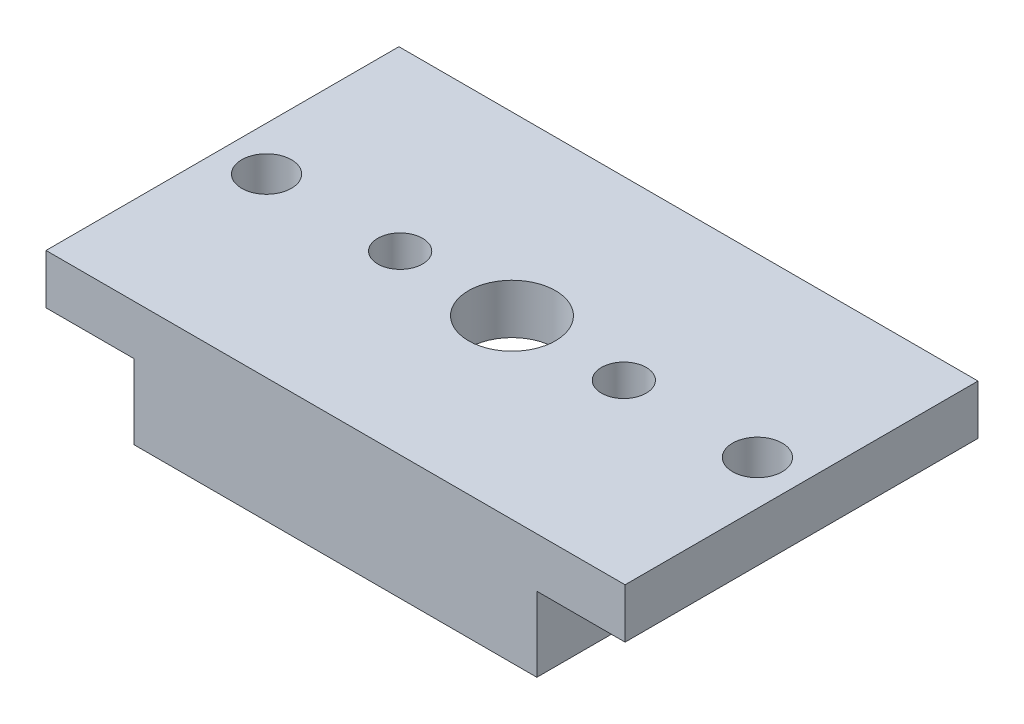
SolidWorks part; units mm, degrees
other "标注1"
sketch "草图3" plane through (-22.25, 4, -10) normal (-0.231, 0.6469, -0.7268) x (-0.9696, -0.2151, 0.1167)
ref_plane "前视基准面" through (0, 0, 0) normal (0, 0, 1) x (1, 0, 0)
ref_plane "上视基准面" through (0, 0, 0) normal (0, 1, 0) x (1, 0, 0)
ref_plane "右视基准面" through (0, 0, 0) normal (1, 0, 0) x (0, 0, -1)
other "Configuration Table"
sketch "草图4" plane through (0, 0, 0) normal (0, 1, 0) x (1, 0, 0)
  line L0 (-4.5, 0) -> (0, 0) construction
  line L1 (-8.1, -7.1) -> (8.1, -7.1)
  line L2 (-8.1, -7.1) -> (-8.1, 7.1)
  line L3 (-8.1, 7.1) -> (8.1, 7.1)
  line L4 (8.1, -7.1) -> (8.1, 7.1)
  line L5 (-8.1, -7.1) -> (8.1, 7.1) construction
  line L6 (-8.1, 7.1) -> (8.1, -7.1) construction
  line L7 (-6.1, 5.1) -> (6.1, 5.1)
  line L8 (-6.1, 5.1) -> (-6.1, -5.1)
  line L9 (-6.1, -5.1) -> (6.1, -5.1)
  line L10 (6.1, 5.1) -> (6.1, -5.1)
  line L11 (0, 0) -> (4.5, 0) construction
  circle A0 centre (0, 0) radius 1.75
  circle A1 centre (-4.5, 0) radius 0.9
  circle A2 centre (4.5, 0) radius 0.9
  point P0 (0, 0)
  dimension "D1" = 2
  dimension "D2" = 2
  dimension "D3" = 3.5
  dimension "D8" = 1.8
  dimension "D9" = 1.8
  dimension "D4" = 2
  dimension "D5" = 2
  dimension "D6" = 12.2
  dimension "D7" = 10.2
  dimension "D10" = 4.5
extrude "凸台-拉伸1" add sketch "草图4" along normal blind 2 contours A2 | L1 L4 L3 L2 | A0 | A1 region at (4.5, 0, 0)
extrude "凸台-拉伸2" add sketch "草图4<8>" against normal blind 3 contours L1 L4 L3 L2 L7 L10 L9 L8 region at (-7.8846, 0, 0)
sketch "草图4<8>" plane through (0, 0, 0) normal (0, 1, 0) x (1, 0, 0) same geometry as "草图4"
sketch "草图5" plane through (0, 2, 0) normal (0, 1, 0) x (1, 0, 0)
  line L0 (-8.1, 7.1) -> (8.1, 7.1) construction
  line L1 (11.65, -7.1) -> (-11.65, -7.1)
  line L2 (11.65, -7.1) -> (11.65, 7.1)
  line L3 (11.65, 7.1) -> (-11.65, 7.1)
  line L4 (-11.65, -7.1) -> (-11.65, 7.1)
  line L5 (-8.1, -7.1) -> (8.1, -7.1) construction
  line L6 (11.65, 0) -> (-11.65, 0) construction
  line L7 (8.1, -7.1) -> (8.1, 7.1) construction
  line L8 (-6.1, 5.1) -> (6.1, 5.1) construction
  line L9 (6.1, 5.1) -> (-6.1, 5.1)
  line L10 (6.1, 5.1) -> (6.1, -5.1)
  line L11 (6.1, -5.1) -> (-6.1, -5.1)
  line L12 (-6.1, 5.1) -> (-6.1, -5.1)
  line L13 (-6.1, -5.1) -> (6.1, -5.1) construction
  line L14 (6.1, 5.1) -> (6.1, -5.1) construction
  line L15 (-6.1, 5.1) -> (-6.1, -5.1) construction
  dimension "D1" = 3.55
extrude "凸台-拉伸3" add sketch "草图5" against normal blind 2
sketch "草图6" plane through (0, 0, 0) normal (0, -1, 0) x (-1, 0, 0)
  line L0 (-11.65, 0) -> (-8.1, 0) construction
  line L1 (-11.65, -7.1) -> (-11.65, 7.1) construction
  line L2 (-8.1, -7.1) -> (-8.1, 7.1) construction
  line L3 (8.1, 0) -> (11.65, 0) construction
  line L4 (8.1, -7.1) -> (8.1, 7.1) construction
  line L5 (11.65, 7.1) -> (11.65, -7.1) construction
  circle A0 centre (-9.875, 0) radius 1
  circle A1 centre (9.875, 0) radius 1
  point P16 (0, 0)
  point P17 (0, 0)
  point P18 (9.875, 0)
  point P19 (9.875, 0)
  point P20 (0, 0)
  dimension "D1" = 2
extrude "切除-拉伸1" cut sketch "草图6" against normal through all
